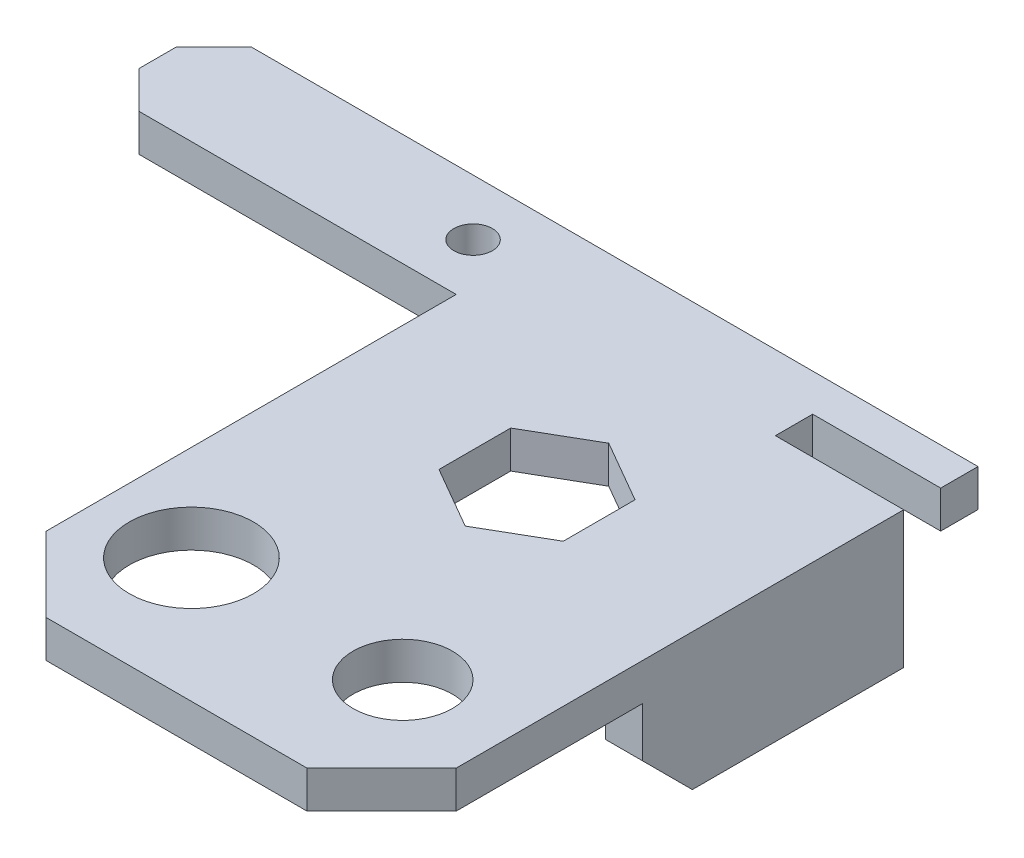
SolidWorks part; units mm, degrees
ref_plane "Alzado" through (0, 0, 0) normal (0, 0, 1) x (1, 0, 0)
ref_plane "Planta" through (0, 0, 0) normal (0, 1, 0) x (1, 0, 0)
ref_plane "Vista lateral" through (0, 0, 0) normal (1, 0, 0) x (0, 0, -1)
sketch "Croquis1" plane through (0, 0, 0) normal (0, 1, 0) x (1, 0, 0)
  line L0 (0, 35) -> (25.3011, 35)
  line L1 (0, 0) -> (0, 35) construction
  line L2 (25.3011, 35) -> (25.3011, -4)
  line L3 (19.3011, -10) -> (-1.6989, -10)
  line L4 (-7.6989, -4) -> (-7.6989, 35)
  line L5 (-7.6989, 35) -> (0, 35)
  line L6 (-1.6989, -10) -> (-7.6989, -4)
  line L7 (25.3011, -4) -> (19.3011, -10)
  circle A0 centre (0, 0) radius 5
  circle A1 centre (17, 0) radius 4
  point P7 (25.3011, -10)
  point P9 (-7.6989, -10)
  dimension "D1" = 10
  dimension "D2" = 8
  dimension "D3" = 17
  dimension "D4" = 35
  dimension "D5" = 45
  dimension "D6" = 33
  dimension "D7" = 7.6989
extrude "Saliente-Extruir1" add sketch "Croquis1" along normal blind 3
sketch "Croquis2" plane through (0, 3, 0) normal (0, 1, 0) x (1, 0, 0)
  line L0 (-7.6989, 38) -> (-7.6989, 29)
  line L1 (-36.1989, 35) -> (-36.1989, 32)
  line L2 (-33.1989, 29) -> (-7.6989, 29)
  line L3 (-7.6989, 35) -> (-7.6989, -4) construction
  line L4 (-36.1989, 32) -> (-33.1989, 29)
  line L5 (-7.6989, 38) -> (-33.1989, 38)
  line L6 (-33.1989, 38) -> (-36.1989, 35)
  point P5 (-36.1989, 29)
  point P8 (-36.1989, 38)
  dimension "D1" = 9
  dimension "D2" = 28.5
  dimension "D3" = 3
extrude "Saliente-Extruir2" add sketch "Croquis2" against normal blind 3
sketch "Croquis3" plane through (0, 3, 0) normal (0, 1, 0) x (1, 0, 0)
  line L0 (25.3011, 35) -> (14.9811, 35)
  line L1 (25.3011, 35) -> (-7.6989, 35) construction
  line L2 (14.9811, 35) -> (14.9811, 32)
  line L3 (14.9811, 32) -> (25.3011, 32)
  line L4 (25.3011, -4) -> (25.3011, 35) construction
  line L5 (25.3011, 35) -> (25.3011, 32)
  dimension "D1" = 3
  dimension "D2" = 10.32
extrude "Cortar-Extruir1" cut sketch "Croquis3" against normal blind 3
sketch "Croquis5" plane through (0, 0, 0) normal (0, -1, 0) x (1, 0, 0)
  line L0 (-7.6989, -29) -> (-7.6989, -11)
  line L1 (-7.6989, -29) -> (-7.6989, 4) construction
  line L2 (-7.6989, -11) -> (-4.6989, -11)
  line L3 (-4.6989, -11) -> (-4.6989, -29)
  line L4 (-4.6989, -29) -> (-4.6989, -32)
  line L5 (-4.6989, -32) -> (-7.6989, -32)
  line L6 (-7.6989, -32) -> (-7.6989, -29)
  dimension "D1" = 3
  dimension "D2" = 18
  dimension "D3" = 3
  dimension "D4" = 18
extrude "Saliente-Extruir3" add sketch "Croquis5" along normal blind 8
sketch "Croquis7" plane through (-7.6989, 0, 0) normal (-1, 0, 0) x (0, 0, 1)
  line L0 (-11, -8) -> (-15, -8)
  line L1 (-11, -8) -> (-32, -8) construction
  line L2 (-15, -8) -> (-11, -4)
  line L3 (-11, -8) -> (-11, 0) construction
  line L4 (-11, -4) -> (-11, -8)
  dimension "D1" = 4
sketch "Croquis11" plane through (0, 0, 0) normal (0, -1, 0) x (1, 0, 0)
  line L0 (25.3011, -32) -> (22.3011, -32)
  line L1 (14.9811, -32) -> (25.3011, -32) construction
  line L2 (22.3011, -32) -> (22.3011, -11)
  line L3 (22.3011, -11) -> (25.3011, -11)
  line L4 (25.3011, 4) -> (25.3011, -32) construction
  line L5 (25.3011, -11) -> (25.3011, -32)
  dimension "D1" = 21
  dimension "D2" = 3
extrude "Saliente-Extruir6" add sketch "Croquis11" along normal blind 8
extrude "Cortar-Extruir3" cut sketch "Croquis7" against normal through all
sketch "Croquis8" plane through (0, 3, 0) normal (0, 1, 0) x (1, 0, 0)
  line L0 (14.9811, 35) -> (25.2811, 35)
  line L1 (14.9811, 35) -> (-7.6989, 35) construction
  line L2 (25.2811, 35) -> (25.2811, 38)
  line L3 (-7.6989, 38) -> (25.2811, 38)
  line L4 (14.9811, 35) -> (-7.6989, 35)
  line L5 (-7.6989, 38) -> (-7.6989, 35)
  dimension "D1" = 10.3
extrude "Saliente-Extruir5" add sketch "Croquis8" against normal blind 3
sketch "Croquis9" plane through (0, 3, 0) normal (0, 1, 0) x (1, 0, 0)
  line L0 (-7.6989, 29) -> (-7.6989, -4) construction
  line L1 (8.8011, 13.2265) -> (13.8011, 16.1132)
  line L2 (13.8011, 16.1132) -> (13.8011, 21.8868)
  line L3 (13.8011, 21.8868) -> (8.8011, 24.7735)
  line L4 (8.8011, 24.7735) -> (3.8011, 21.8868)
  line L5 (3.8011, 21.8868) -> (3.8011, 16.1132)
  line L6 (3.8011, 16.1132) -> (8.8011, 13.2265)
  line L8 (-33.1989, 29) -> (-7.6989, 29) construction
  circle A0 centre (8.8011, 19) radius 5 construction
  dimension "D3" = 10
  dimension "D1" = 16.5
  dimension "D2" = 10
extrude "Cortar-Extruir4" cut sketch "Croquis9" against normal blind 3
sketch "Croquis10" plane through (0, 3, 0) normal (0, 1, 0) x (1, 0, 0)
  line L0 (-36.1989, 35) -> (-36.1989, 32) construction
  line L1 (25.2811, 38) -> (-33.1989, 38) construction
  circle A0 centre (-10.8389, 33.5) radius 1.55
  dimension "D1" = 3.1
  dimension "D2" = 25.36
  dimension "D3" = 4.5
extrude "Cortar-Extruir5" cut sketch "Croquis10" against normal blind 3
